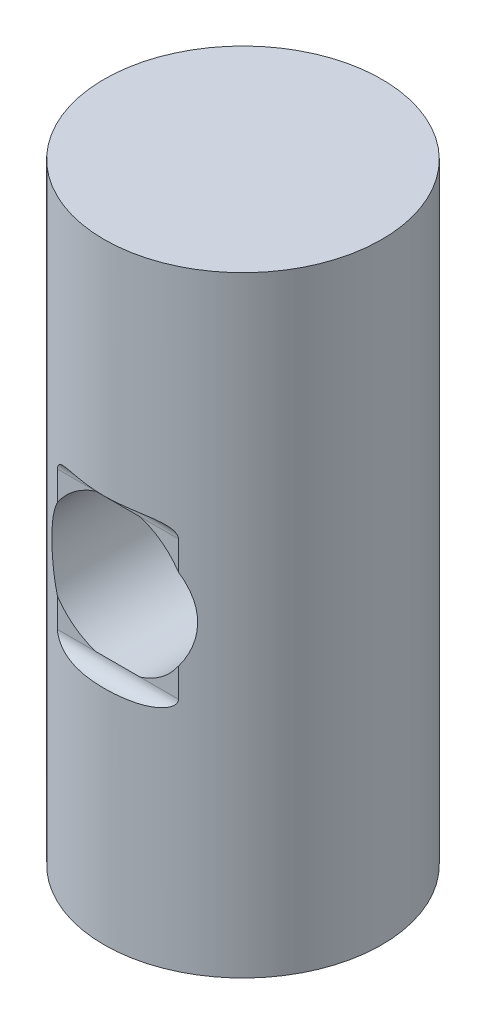
SolidWorks part; units mm, degrees
ref_plane "正面" through (0, 0, 0) normal (0, 0, 1) x (1, 0, 0)
ref_plane "平面" through (0, 0, 0) normal (0, 1, 0) x (1, 0, 0)
ref_plane "右側面" through (0, 0, 0) normal (1, 0, 0) x (0, 0, -1)
sketch "ｽｹｯﾁ1" plane through (0, 0, 0) normal (0, 1, 0) x (1, 0, 0)
  circle A0 centre (0, 0) radius 10
  dimension "D1" = 20
extrude "ﾎﾞｽ - 押し出し1" add sketch "ｽｹｯﾁ1" along normal mid plane 44
sketch "ｽｹｯﾁ4" plane through (0, 0, 0) normal (1, 0, 0) x (0, 0, -1)
  line L0 (-10, -22) -> (10, -22) construction
  line L1 (-12.5256, 6) -> (-9, 6)
  line L2 (-12.5256, 6) -> (-12.5256, -6)
  line L3 (-12.5256, -6) -> (-9, -6)
  line L4 (-9, 6) -> (-9, -6)
  line L5 (0, 24.8415) -> (0, -25.9203) construction
  line L6 (9, 6) -> (9, -6)
  line L7 (12.5256, -6) -> (9, -6)
  line L8 (12.5256, 6) -> (12.5256, -6)
  line L10 (12.5256, 6) -> (9, 6)
  dimension "D1" = 12
  dimension "D2" = 16
  dimension "D3" = 9
extrude "ｶｯﾄ - 押し出し1" cut sketch "ｽｹｯﾁ4" against normal mid plane 44
fillet "ﾌｨﾚｯﾄ1" radius 1 4 edges at (0, -6, -9) (0, 6, -9) (0, -6, 9) (0, 6, 9)
sketch "Sketch1" plane through (0, 0, 9) normal (0, 0, 1) x (1, 0, 0)
  point P0 (0, 0)
hole_wizard "M12x1.5 ねじ穴1" positions "Sketch3" profile "Sketch2" tap size "M12x1.5" standard "JIS" end condition through all
sketch "Sketch3" plane through (0, 0, 9) normal (0, 0, 1) x (1, 0, 0)
  point P1 (0, 0)
sketch "Sketch2" plane through (0, 0, 9) normal (1, 0, 0) x (0, -1, 0)
  line L0 (0, 0) -> (0, 19)
  line L1 (0, 19) -> (5.25, 19)
  line L2 (5.25, 19) -> (5.25, 0)
  line L5 (5.25, 0) -> (0, 0)
  line L11 (0, -6.35) -> (0, 107.95) construction
  dimension "Thru Tap Drill Dia." = 10.5
  dimension "Thru Tap Drill Depth" = 19
cosmetic thread "Hole Thread1" parameters "D2"=12
